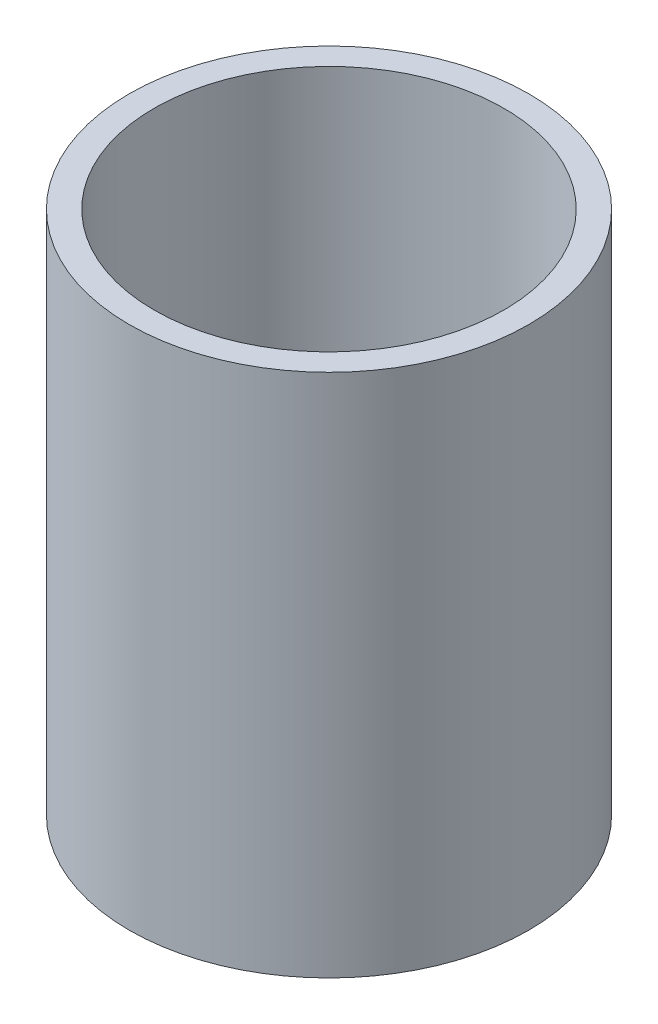
SolidWorks part; units mm, degrees
ref_plane "Front Plane" through (0, 0, 0) normal (0, 0, 1) x (1, 0, 0)
ref_plane "Top Plane" through (0, 0, 0) normal (0, 1, 0) x (1, 0, 0)
ref_plane "Right Plane" through (0, 0, 0) normal (1, 0, 0) x (0, 0, -1)
sketch "Sketch1" plane through (0, 0, 0) normal (0, 1, 0) x (1, 0, 0)
  circle A0 centre (0, 0) radius 40
  dimension "D1" = 80
extrude "Boss-Extrude1" add sketch "Sketch1" along normal blind 5
sketch "Sketch4" plane through (0, 5, 0) normal (0, 1, 0) x (1, 0, 0)
  circle A0 centre (-7.5, 0) radius 2
  circle A1 centre (7.5, 0) radius 2
  dimension "D1" = 4
  dimension "D2" = 4
  dimension "D3" = 7.5
  dimension "D4" = 7.5
extrude "Cut-Extrude1" cut sketch "Sketch4" against normal up to surface (5 mm away) up to face at (0, 0, 40)
sketch "Sketch5" plane through (0, 5, 0) normal (0, 1, 0) x (1, 0, 0)
  circle A0 centre (0, 0) radius 40
  circle A1 centre (0, 0) radius 35
  dimension "D1" = 5
extrude "Boss-Extrude2" add sketch "Sketch5" along normal blind 100
sketch "Sketch6" plane through (0, 5, 0) normal (0, 1, 0) x (1, 0, 0)
  circle A0 centre (0, 0) radius 2
extrude "Boss-Extrude3" add sketch "Sketch6" along normal blind 20
sketch "Sketch7" plane through (0, 5, 0) normal (0, 1, 0) x (1, 0, 0)
  circle A1 centre (0, -27) radius 3.5
  point P0 (0, 0)
  dimension "D1" = 27
extrude "Cut-Extrude2" cut sketch "Sketch7" against normal blind 5
